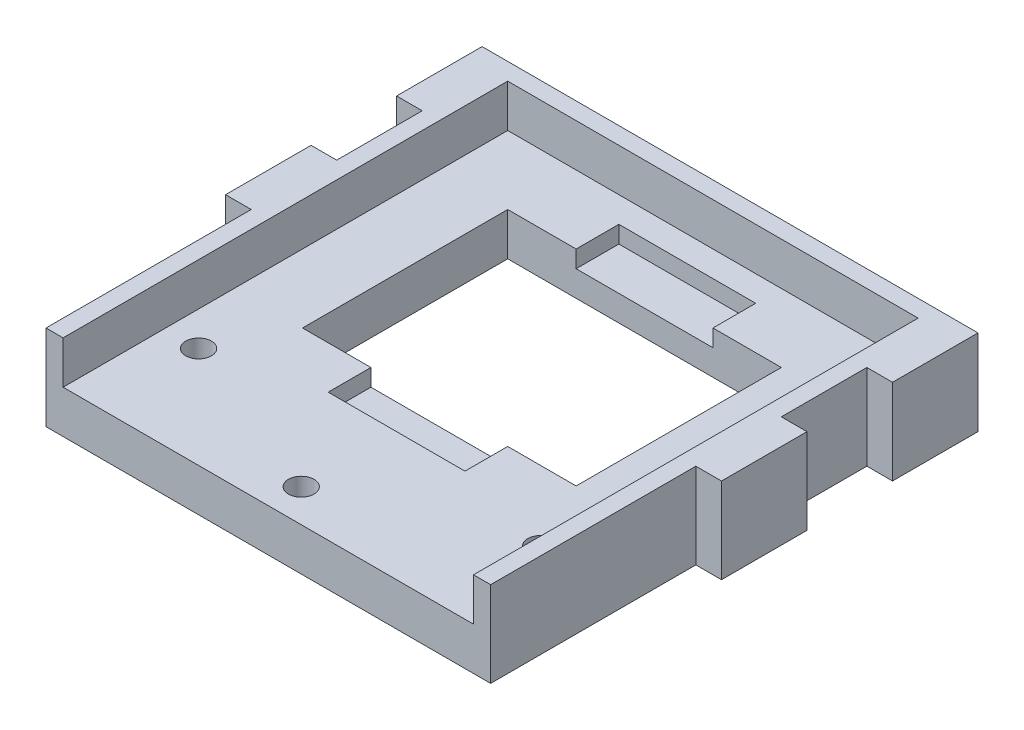
SolidWorks part; units mm, degrees
ref_plane "Front Plane" through (0, 0, 0) normal (0, 0, 1) x (1, 0, 0)
ref_plane "Top Plane" through (0, 0, 0) normal (0, 1, 0) x (1, 0, 0)
ref_plane "Right Plane" through (0, 0, 0) normal (1, 0, 0) x (0, 0, -1)
sketch "Sketch1" plane through (0, 0, 0) normal (0, 1, 0) x (1, 0, 0)
  line L0 (0, -1000) -> (0, 49000) construction
  line L1 (-26, -27) -> (26, -27)
  line L2 (-26, -27) -> (-26, 27)
  line L3 (-26, 27) -> (26, 27)
  line L4 (26, -27) -> (26, 27)
  line L5 (-26, -27) -> (26, 27) construction
  line L6 (-26, 27) -> (26, -27) construction
  line L7 (-16, 17) -> (16, 17)
  line L8 (-16, 17) -> (-16, -7)
  line L9 (-16, -7) -> (16, -7)
  line L10 (16, 17) -> (16, -7)
  line L11 (-16, 17) -> (16, -7) construction
  line L12 (-16, -7) -> (16, 17) construction
  point P0 (0, 0)
  point P6 (0, 5)
  dimension "D1" = 54
  dimension "D2" = 52
  dimension "D3" = 24
  dimension "D4" = 32
extrude "Boss-Extrude1" add sketch "Sketch1" along normal blind 10
sketch "Sketch2" plane through (0, 10, 0) normal (0, 1, 0) x (-1, 0, 0)
  line L0 (26, 27) -> (-26, 27) construction
  line L1 (24, 27) -> (-24, 27)
  line L2 (24, 27) -> (24, -25)
  line L3 (24, -25) -> (-24, -25)
  line L4 (-24, 27) -> (-24, -25)
  line L5 (-24, -25) -> (24, 27) construction
  line L7 (0, 0) -> (0, 41.3981) construction
  line L8 (-26, -27) -> (26, -27) construction
  point P7 (0, 1)
  dimension "D1" = 2
  dimension "D2" = 48
extrude "Cut-Extrude1" cut sketch "Sketch2" against normal blind 5
sketch "Sketch3" plane through (0, 5, 0) normal (0, 1, 0) x (-1, 0, 0)
  line L0 (16, -17) -> (-16, -17) construction
  line L1 (8, -17) -> (-8, -17)
  line L2 (8, -17) -> (8, -22)
  line L3 (8, -22) -> (-8, -22)
  line L4 (-8, -17) -> (-8, -22)
  line L5 (-16, 7) -> (16, 7) construction
  line L6 (8, 7) -> (-8, 7)
  line L7 (8, 7) -> (8, 12)
  line L8 (8, 12) -> (-8, 12)
  line L9 (-8, 7) -> (-8, 12)
  line L10 (16, -17) -> (-16, 7) construction
  line L11 (8, 12) -> (-8, -22) construction
  point P16 (0, -5)
  point P17 (0, -5)
  dimension "D1" = 5
  dimension "D2" = 16
extrude "Cut-Extrude2" cut sketch "Sketch3" against normal blind 2
sketch "Sketch4" plane through (0, 5, 0) normal (0, 1, 0) x (1, 0, 0)
  line L0 (24, -27) -> (24, 25) construction
  line L1 (-24, -27) -> (24, -27) construction
  line L2 (-24, -27) -> (-24, -12) construction
  line L3 (-24, -12) -> (24, -12) construction
  line L4 (24, -27) -> (24, -12) construction
  line L5 (-8, -12) -> (8, -12) construction
  line L6 (-20, -15.1524) -> (20, -15.1524) construction
  line L7 (0, 0) -> (0, -23.1524) construction
  circle A0 centre (-20, -15.1524) radius 1.5
  circle A1 centre (0, -23.1524) radius 1.5
  circle A2 centre (20, -15.1524) radius 1.5
  point P16 (0, -15.1524)
  dimension "D1" = 3
  dimension "D2" = 40
  dimension "D3" = 8
extrude "Cut-Extrude3" cut sketch "Sketch4" against normal blind 5
sketch "Sketch5" [suppressed] plane through (0, 0, 0) normal (0, -1, 0) x (1, 0, 0)
  line L0 (-26, 27) -> (26, 27) construction
  line L1 (-16, 7) -> (16, 7)
  line L2 (-16, 7) -> (-16, 27)
  line L3 (-16, 27) -> (16, 27)
  line L4 (16, 7) -> (16, 27)
  line L5 (16, 7) -> (16, -17) construction
extrude "Cut-Extrude4" [suppressed] cut sketch "Sketch5" against normal blind 10
sketch "Sketch6" plane through (0, 10, 0) normal (0, 1, 0) x (1, 0, 0)
  line L1 (-26, 27) -> (-29, 27)
  line L2 (-26, 27) -> (-26, 17)
  line L3 (-26, 17) -> (-29, 17)
  line L4 (-29, 27) -> (-29, 17)
  dimension "D1" = 3
  dimension "D2" = 10
extrude "Boss-Extrude2" add sketch "Sketch6" against normal blind 10
pattern_linear "LPattern1" count 2 spacing 20 along (0, 0, 1) of "Boss-Extrude2"
mirror "Mirror1" about plane through (0, 0, 0) normal (1, 0, 0) of "LPattern1"
